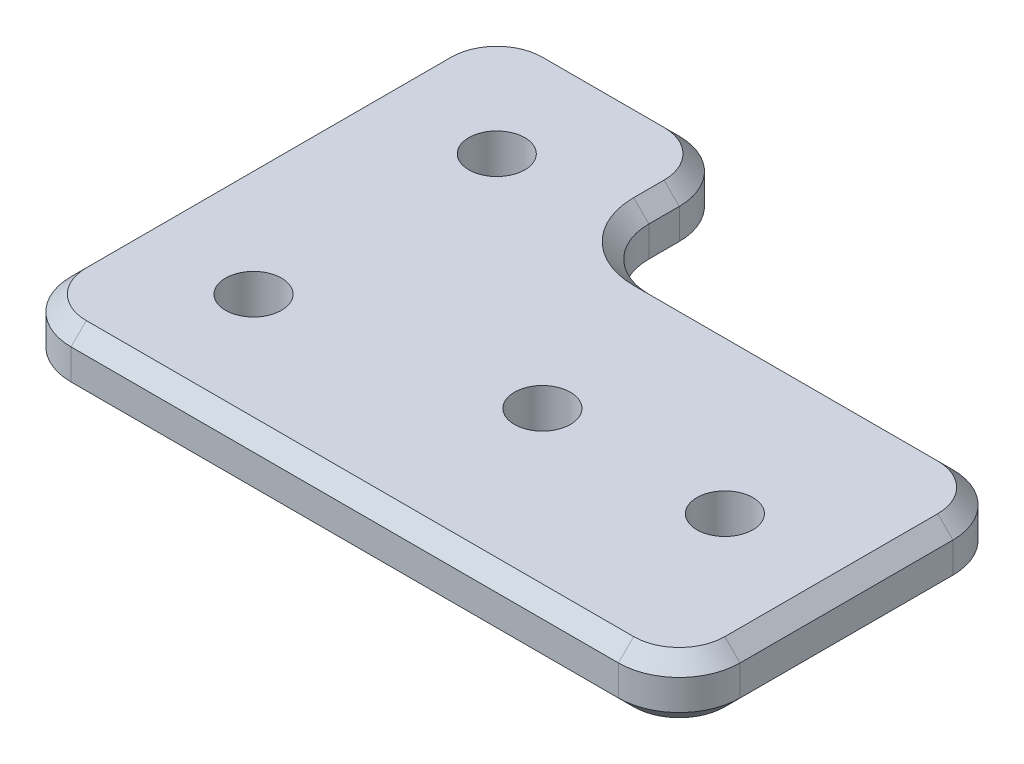
SolidWorks part; units mm, degrees
ref_plane "Front Plane" through (0, 0, 0) normal (0, 0, 1) x (1, 0, 0)
ref_plane "Top Plane" through (0, 0, 0) normal (0, 1, 0) x (1, 0, 0)
ref_plane "Right Plane" through (0, 0, 0) normal (1, 0, 0) x (0, 0, -1)
sketch "Sketch1" plane through (0, 0, 0) normal (0, 0, 1) x (1, 0, 0)
  line L13 (0, 0) -> (69.85, 0)
  line L14 (0, 0) -> (0, 6.35)
  line L15 (0, 6.35) -> (69.85, 6.35)
  line L16 (69.85, 0) -> (69.85, 6.35)
  dimension "D1" = 69.85
  dimension "D2" = 6.35
extrude "Boss-Extrude1" add sketch "Sketch1" along normal mid plane 50.8
sketch "Sketch2" plane through (0, 6.35, 0) normal (0, 1, 0) x (1, 0, 0)
  line L0 (69.85, 0) -> (0, 0) construction
  line L1 (69.85, -25.4) -> (69.85, 25.4) construction
  line L2 (0, -25.4) -> (0, 25.4) construction
  circle A0 centre (12.7, 12.7) radius 2.921
  circle A1 centre (12.7, -12.7) radius 2.921
  dimension "D1" = 5.842
  dimension "D2" = 12.7
  dimension "D3" = 12.7
extrude "Cut-Extrude1" cut sketch "Sketch2" against normal through all
sketch "Sketch3" plane through (0, 6.35, 0) normal (0, 1, 0) x (1, 0, 0)
  line L0 (0, -25.4) -> (0, 25.4) construction
  line L1 (69.85, 25.4) -> (25.4, 25.4)
  line L2 (69.85, 25.4) -> (69.85, 9.525)
  line L3 (69.85, 9.525) -> (25.4, 9.525)
  line L4 (25.4, 25.4) -> (25.4, 9.525)
  dimension "D1" = 25.4
  dimension "D2" = 15.875
extrude "Cut-Extrude2" cut sketch "Sketch3" against normal through all
fillet "Fillet1" radius 6.35 6 edges at (0, 3.175, 25.4) (0, 3.175, -25.4) (25.4, 3.175, -25.4) (25.4, 3.175, -9.525) (69.85, 3.175, 25.4) (69.85, 3.175, -9.525)
chamfer "Chamfer2" distance 1.5875 angle 45 24 edges at (1.8599, 0, 23.5401) (34.925, 0, 25.4) (67.9901, 0, 23.5401) (69.85, 0, 7.9375) (67.9901, 0, -7.6651) (47.625, 0, -9.525) (27.2599, 0, -11.3849) (25.4, 0, -17.4625) (23.5401, 0, -23.5401) (12.7, 0, -25.4) (0, 0, 0) (1.8599, 0, -23.5401) (1.8599, 6.35, 23.5401) (34.925, 6.35, 25.4) (67.9901, 6.35, 23.5401) (69.85, 6.35, 7.9375) (67.9901, 6.35, -7.6651) (47.625, 6.35, -9.525) (27.2599, 6.35, -11.3849) (25.4, 6.35, -17.4625) (23.5401, 6.35, -23.5401) (12.7, 6.35, -25.4) (1.8599, 6.35, -23.5401) (0, 6.35, 0)
sketch "Sketch4" plane through (0, 6.35, 0) normal (0, 1, 0) x (1, 0, 0)
  line L0 (68.2625, -7.9375) -> (1.5875, -7.9375) construction
  line L1 (68.2625, -19.05) -> (68.2625, 3.175) construction
  line L2 (1.5875, 19.05) -> (1.5875, -19.05) construction
  line L4 (0, -19.05) -> (0, 19.05) construction
  circle A0 centre (57.15, -7.9375) radius 2.921
  circle A1 centre (38.1, -7.9375) radius 2.921
  dimension "D1" = 5.842
  dimension "D2" = 38.1
  dimension "D3" = 19.05
extrude "Cut-Extrude3" cut sketch "Sketch4" against normal through all
